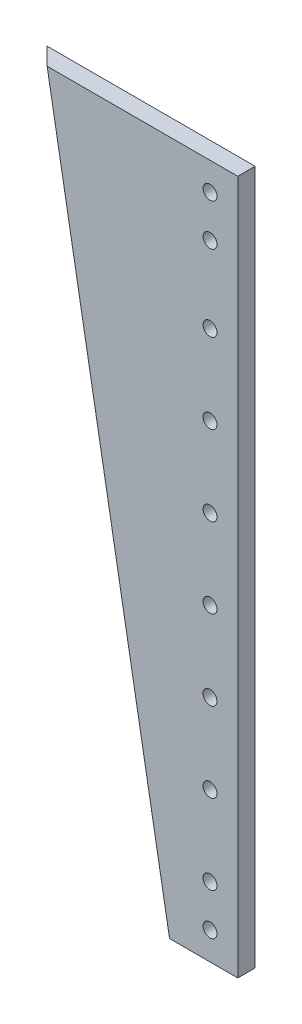
SolidWorks part; units mm, degrees
ref_plane "Front Plane" through (0, 0, 0) normal (0, 0, 1) x (1, 0, 0)
ref_plane "Top Plane" through (0, 0, 0) normal (0, 1, 0) x (1, 0, 0)
ref_plane "Right Plane" through (0, 0, 0) normal (1, 0, 0) x (0, 0, -1)
sketch "Sketch1" plane through (0, 0, 0) normal (0, 0, 1) x (1, 0, 0)
  line L1 (-60, 200) -> (0, 200)
  line L2 (-60, 200) -> (-60, 0)
  line L3 (-60, 0) -> (0, 0)
  line L4 (0, 200) -> (0, 0)
  dimension "D1" = 60
  dimension "D2" = 200
extrude "Boss-Extrude1" add sketch "Sketch1" along normal blind 5
sketch "Sketch6" plane through (0, 0, 0) normal (0, 0, 1) x (1, 0, 0)
  line L0 (-60, 0) -> (0, 0) construction
  line L1 (0, 0) -> (0, 200) construction
  circle A0 centre (-8, 8) radius 2
  circle A1 centre (-8, 20) radius 2
  dimension "D1" = 4
  dimension "D2" = 8
  dimension "D3" = 12
  dimension "D4" = 8
extrude "Cut-Extrude3" cut sketch "Sketch6" along normal up to surface (5 mm away) up to face at (-30, 100, 5)
ref_plane "Plane1" through (0, 100, 0) normal (0, 1, 0) x (1, 0, 0)
mirror "Mirror1" about plane through (0, 100, 0) normal (0, 1, 0) of "Cut-Extrude3"
sketch "Sketch7" plane through (0, 0, 0) normal (0, 0, 1) x (1, 0, 0)
  line L0 (-8, 43) -> (-8, 20) construction
  circle A0 centre (-8, 43) radius 2
  dimension "D2" = 4
  dimension "D1" = 23
extrude "Cut-Extrude4" cut sketch "Sketch7" along normal up to surface (5 mm away) up to face at (-6, 192, 5)
pattern_linear "LPattern1" count 6 spacing 23 along (0, 1, 0) of "Cut-Extrude4"
sketch "Sketch3" plane through (-200, 0, 0) normal (0, 0, -1) x (-1, 0, 0)
  line L8 (-140, 0) -> (-175.2654, 0)
  line L9 (-140, 0) -> (-200, 0) construction
  line L10 (-140, 200) -> (-140, 0) construction
  line L11 (-175.2654, 0) -> (-140, 200)
  line L12 (-140, 200) -> (-140, 0)
  line L13 (-154.1062, 0) -> (-154.1062, 120) construction
  dimension "D1" = 10
  dimension "D2" = 120
extrude "傾斜刀" cut sketch "Sketch3" against normal up to surface (5 mm away) up to face at (-6, 66, 5)
chamfer "傾斜刀倒角" distance 5 angle 45 1 edges at (-42.3673, 100, 5)
chamfer "垂直刀倒角" [suppressed] distance 5 angle 45
